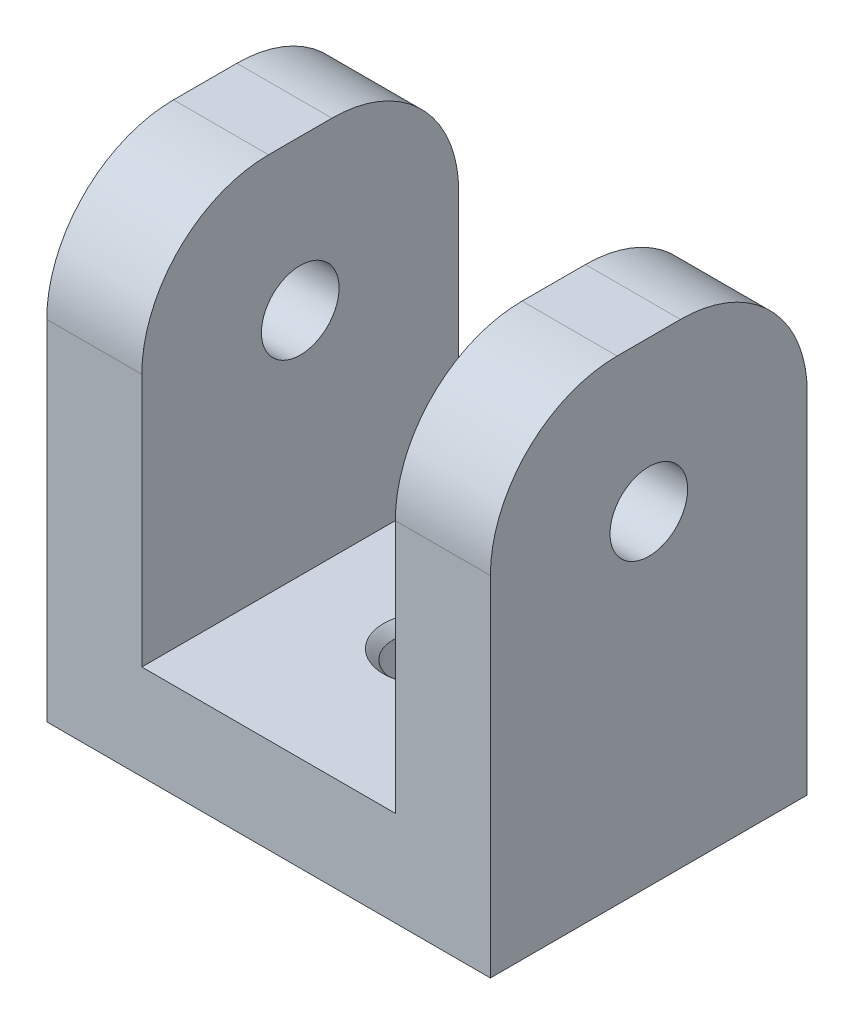
SolidWorks part; units mm, degrees
ref_plane "Front Plane" through (0, 0, 0) normal (0, 0, 1) x (1, 0, 0)
ref_plane "Top Plane" through (0, 0, 0) normal (0, 1, 0) x (1, 0, 0)
ref_plane "Right Plane" through (0, 0, 0) normal (1, 0, 0) x (0, 0, -1)
sketch "Sketch1" plane through (0, 0, 0) normal (0, 1, 0) x (1, 0, 0)
  line L1 (0, 0) -> (28, 0)
  line L2 (0, 0) -> (0, -20)
  line L3 (0, -20) -> (28, -20)
  line L4 (28, 0) -> (28, -20)
  dimension "D1" = 20
  dimension "D2" = 28
extrude "Boss-Extrude1" add sketch "Sketch1" along normal blind 6
sketch "Sketch2" plane through (0, 6, 0) normal (0, 1, 0) x (1, 0, 0)
  line L0 (0, -20) -> (28, -20) construction
  line L1 (0, 0) -> (6, 0)
  line L2 (0, 0) -> (0, -20)
  line L3 (0, -20) -> (6, -20)
  line L4 (6, 0) -> (6, -20)
  line L6 (28, 0) -> (22, 0)
  line L7 (28, 0) -> (28, -20)
  line L8 (28, -20) -> (22, -20)
  line L9 (22, 0) -> (22, -20)
  dimension "D1" = 16
  dimension "D2" = 6
extrude "Boss-Extrude2" add sketch "Sketch2" along normal blind 24
sketch "Sketch3" plane through (6, 0, 0) normal (1, 0, 0) x (0, 0, -1)
  line L0 (-20, 6) -> (0, 6) construction
  line L1 (-20, 30) -> (-20, 6) construction
  circle A0 centre (-10, 20.5) radius 2.45
  dimension "D3" = 4.9
  dimension "D1" = 14.5
  dimension "D2" = 10
extrude "Cut-Extrude1" cut sketch "Sketch3" against normal through all both and the other way through all
sketch "Sketch4" plane through (0, 6, 0) normal (0, 1, 0) x (1, 0, 0)
  circle A0 centre (14, -10) radius 1.65
  dimension "D1" = 3.3
extrude "Cut-Extrude2" cut sketch "Sketch4" against normal through all
sketch "Sketch5" plane through (0, 6, 0) normal (0, 1, 0) x (1, 0, 0)
  circle A0 centre (14, -10) radius 2.15
  dimension "D1" = 4.3
extrude "Cut-Extrude3" cut sketch "Sketch5" against normal blind 3
fillet "Fillet1" radius 0.6 1 edges at (14, 6, 12.15) conic rho 0.05
ref_plane "打印面" through (0, 0, -10) normal (0, 0, 1) x (1, 0, 0)
fillet "Fillet2" radius 8 4 edges at (3, 30, 20) (3, 30, 0) (25, 30, 0) (25, 30, 20)
equation "\"D2@Sketch2\"=\"D2@Sketch1\"/2-\"D1@Sketch2\"/2"
equation "\"D1@Sketch3\"=14.5"
equation "\"D2@Sketch3\"=\"D1@Sketch1\"/2"
equation "\"滑动-垂直孔\"= 0.6"
equation "\"滑动-水平孔\"= 0.3"
equation "\"松动-垂直孔\"= 0.3"
equation "\"松动-水平孔\"= 0.1"
equation "\"正常-垂直孔\"= 0.15"
equation "\"正常-水平孔\"= 0"
equation "\"紧缩-垂直孔\"= 0"
equation "\"紧缩-水平孔\"= - 0.1"
equation "\"D3@Sketch3\"=\"紧缩-水平孔\"+5"
equation "\"D1@Sketch4\"=\"松动-垂直孔\"+3"
equation "\"D1@Sketch5\"=\"松动-垂直孔\"+4"
